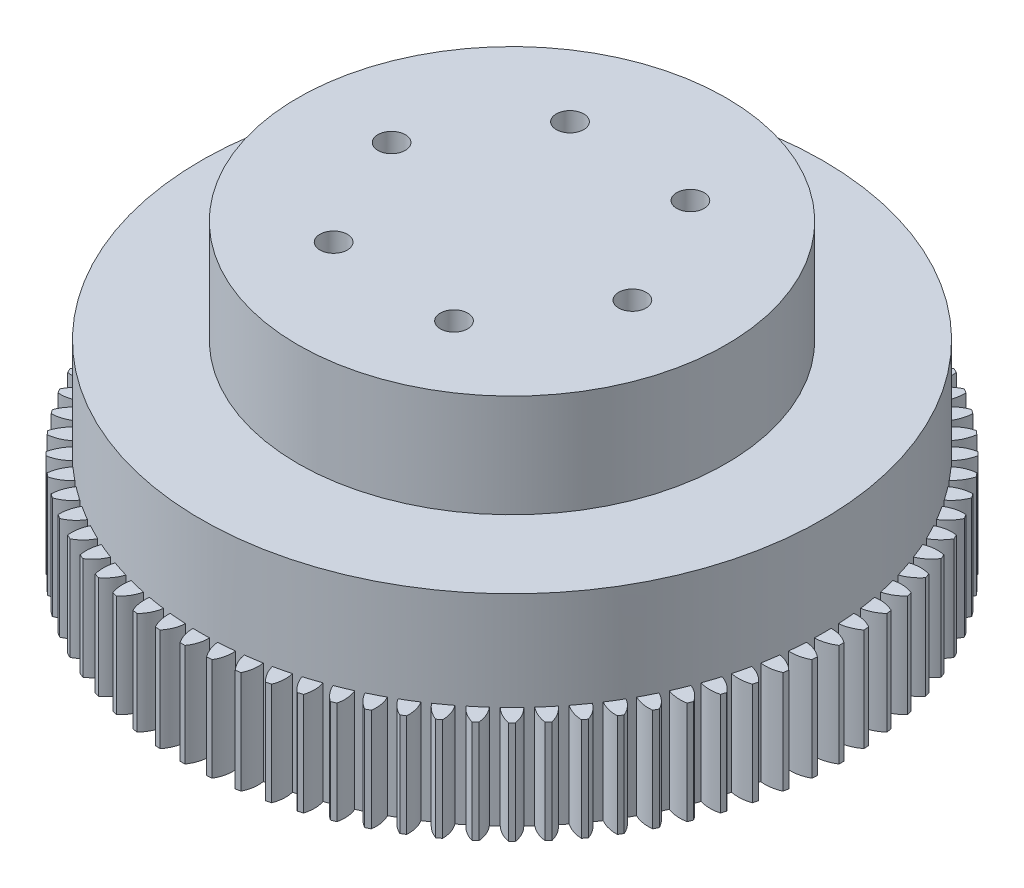
SolidWorks part; units mm, degrees
ref_plane "Front Plane" through (0, 0, 0) normal (0, 0, 1) x (1, 0, 0)
ref_plane "Top Plane" through (0, 0, 0) normal (0, 1, 0) x (1, 0, 0)
ref_plane "Right Plane" through (0, 0, 0) normal (1, 0, 0) x (0, 0, -1)
sketch "Sketch1" plane through (0, 0, 0) normal (0, 1, 0) x (1, 0, 0)
  circle A0 centre (0, 0) radius 25
  dimension "D1" = 50
extrude "Boss-Extrude4" add sketch "Sketch1" along normal blind 12
sketch "Sketch16" plane through (0, 0, 0) normal (0, -1, 0) x (1, 0, 0)
  circle A0 centre (0, 0) radius 36.3
  dimension "D1" = 72.6
extrude "Boss-Extrude5" add sketch "Sketch16" along normal blind 23.5
sketch "Sketch17" plane through (0, -23.5, 0) normal (0, -1, 0) x (1, 0, 0)
  line L5 (-0.2925, 38.48) -> (0.2927, 38.48)
  arc A5 (-0.9725, 36.2) -> (0.9727, 36.1955) centre (-0.0573, 11.1978) cw
  arc A6 (-0.9725, 36.2) -> (-0.2925, 38.48) centre (3.1899, 36.2) cw
  arc A7 (0.9727, 36.1955) -> (0.2927, 38.48) centre (-2.7147, 36.3414) ccw
  dimension "D6" = 1.9451
  dimension "D1" = 2.28
  dimension "D2" = 0.68
  dimension "D3" = 0.68
  dimension "D4" = 0.5851
  dimension "D5" = 2.2845
  dimension "D7" = 36.2
extrude "Boss-Extrude6" add sketch "Sketch17" against normal blind 12
pattern_circular "CirPattern1" count 80 over 360 about axis through (0, -23.5, 0) along (0, 1, 0) of "Boss-Extrude6"
sketch "Sketch18" plane through (0, 12, 0) normal (0, 1, 0) x (1, 0, 0)
  circle A0 centre (-15, 0.9398) radius 1.6
  circle A1 centre (-6.6861, 13.4603) radius 1.6
  circle A2 centre (8.3139, 12.5205) radius 1.6
  circle A3 centre (15, -0.9398) radius 1.6
  circle A4 centre (6.6861, -13.4603) radius 1.6
  circle A5 centre (-8.3139, -12.5205) radius 1.6
  point P15 (0, 0)
  dimension "D1" = 3.2
  dimension "D2" = 15
  dimension "D3" = 6
extrude "Cut-Extrude1" cut sketch "Sketch18" against normal through all
sketch "Sketch19" plane through (0, -23.5, 0) normal (0, -1, 0) x (1, 0, 0)
  circle A0 centre (15, 0.9398) radius 4
  circle A1 centre (8.3139, -12.5205) radius 4
  circle A2 centre (-6.6861, -13.4603) radius 4
  circle A3 centre (-15, -0.9398) radius 4
  circle A4 centre (-8.3139, 12.5205) radius 4
  circle A5 centre (6.6861, 13.4603) radius 4
  point P15 (0, 0)
  dimension "D1" = 8
  dimension "D2" = 6
extrude "Cut-Extrude2" cut sketch "Sketch19" against normal blind 32
